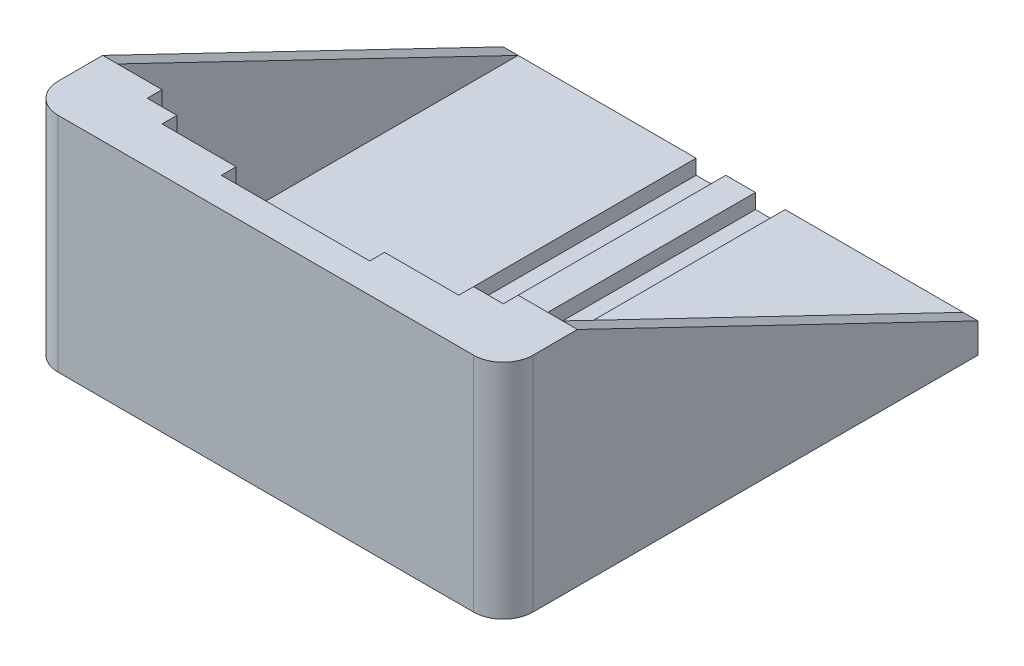
SolidWorks part; units mm, degrees
ref_plane "Front Plane" through (0, 0, 0) normal (0, 0, 1) x (1, 0, 0)
ref_plane "Top Plane" through (0, 0, 0) normal (0, 1, 0) x (1, 0, 0)
ref_plane "Right Plane" through (0, 0, 0) normal (1, 0, 0) x (0, 0, -1)
sketch "Sketch1" plane through (0, 0, 0) normal (0, 1, 0) x (1, 0, 0)
  line L1 (-80, 80) -> (80, 80)
  line L2 (-80, 80) -> (-80, -80)
  line L3 (-80, -80) -> (80, -80)
  line L4 (80, 80) -> (80, -80)
  line L5 (-80, 80) -> (80, -80) construction
  line L6 (-80, -80) -> (80, 80) construction
  point P0 (0, 0)
  dimension "D1" = 160
  dimension "D2" = 160
extrude "Boss-Extrude1" add sketch "Sketch1" along normal blind 75
sketch "Sketch2" plane through (0, 75, 0) normal (0, 1, 0) x (1, 0, 0)
  line L0 (-80, 80) -> (-80, -80) construction
  line L2 (-75, 80) -> (75, 80)
  line L4 (-75, 80) -> (-75, -70)
  line L5 (-75, -70) -> (75, -70)
  line L6 (75, 80) -> (75, -70)
  line L7 (80, -80) -> (80, 80) construction
  line L8 (80, 80) -> (-80, 80) construction
  line L9 (-80, -80) -> (80, -80) construction
  point P6 (0, 0)
  point P13 (0, 0)
  dimension "D1" = 5
  dimension "D2" = 5
  dimension "D3" = 0
  dimension "D4" = 10
extrude "Cut-Extrude1" cut sketch "Sketch2" against normal offset from surface (65 mm away) 10 up to face at (0, 0, 0)
sketch "Sketch3" plane through (0, 0, 70) normal (0, 0, -1) x (-1, 0, 0)
  line L0 (-75, 10) -> (75, 10) construction
  line L1 (-75, 75) -> (-60, 75)
  line L2 (-75, 75) -> (-75, 10)
  line L3 (-75, 10) -> (-60, 10)
  line L4 (-60, 75) -> (-60, 10)
  line L5 (0, 75) -> (0, 10) construction
  line L6 (75, 75) -> (-75, 75) construction
  line L7 (75, 10) -> (60, 10)
  line L8 (60, 75) -> (60, 10)
  line L9 (75, 75) -> (60, 75)
  line L10 (75, 75) -> (75, 10)
  dimension "D1" = 15
extrude "Boss-Extrude2" add sketch "Sketch3" along normal blind 15
sketch "Sketch4" plane through (0, 0, 70) normal (0, 0, -1) x (-1, 0, 0)
  line L0 (0, 75) -> (0, 10) construction
  line L1 (60, 75) -> (-60, 75) construction
  line L2 (75, 10) -> (-75, 10) construction
  line L3 (-60, 10) -> (60, 10) construction
  line L4 (-60, 75) -> (-50, 75)
  line L5 (-60, 75) -> (-60, 10)
  line L6 (-60, 10) -> (-50, 10)
  line L7 (-50, 75) -> (-50, 10)
  line L8 (60, 10) -> (50, 10)
  line L9 (50, 75) -> (50, 10)
  line L10 (60, 75) -> (50, 75)
  line L11 (60, 75) -> (60, 10)
  dimension "D1" = 10
extrude "Boss-Extrude3" add sketch "Sketch4" along normal blind 10
fillet "Fillet1" radius 10 2 edges at (80, 37.5, 80) (-80, 37.5, 80)
sketch "Sketch11" plane through (0, 0, 70) normal (0, 0, -1) x (-1, 0, 0)
  line L0 (-50, 10) -> (50, 10) construction
  line L1 (-50, 75) -> (-25, 75)
  line L2 (-50, 75) -> (-50, 10)
  line L3 (-50, 10) -> (-25, 10)
  line L4 (-25, 75) -> (-25, 10)
  line L5 (0, 75) -> (0, 10) construction
  line L6 (50, 75) -> (-50, 75) construction
  line L7 (75, 10) -> (-75, 10) construction
  line L8 (50, 10) -> (25, 10)
  line L9 (25, 75) -> (25, 10)
  line L10 (50, 75) -> (25, 75)
  line L11 (50, 75) -> (50, 10)
  dimension "D1" = 25
extrude "Boss-Extrude4" add sketch "Sketch11" along normal blind 5
fillet "Fillet2" radius 30 2 edges at (-77.5, 75, -80) (77.5, 75, -80)
sketch "Sketch15" plane through (0, 0, 0) normal (0, -1, 0) x (1, 0, 0)
  line L0 (-80, 40) -> (80, 40) construction
  line L1 (80, 70) -> (80, -80) construction
  line L2 (25, 70) -> (-25, 70) construction
  line L4 (-80, -80) -> (-80, 70) construction
  circle A0 centre (-60, 50) radius 1.5
  circle A1 centre (-40, 50) radius 1.5
  circle A2 centre (40, 50) radius 1.5
  circle A3 centre (60, 50) radius 1.5
  circle A4 centre (60, 30) radius 1.5
  circle A5 centre (40, 30) radius 1.5
  circle A6 centre (-40, 30) radius 1.5
  circle A7 centre (-60, 30) radius 1.5
  point P6 (0, 0)
  dimension "D1" = 3
  dimension "D2" = 3
  dimension "D11" = 3
  dimension "D12" = 3
  dimension "D3" = 20
  dimension "D4" = 10
  dimension "D5" = 20
  dimension "D6" = 10
  dimension "D7" = 10
  dimension "D8" = 20
  dimension "D9" = 20
  dimension "D10" = 30
extrude "Cut-Extrude2" cut sketch "Sketch15" against normal up to surface (10 mm away) up to face at (0, 10, 43.75)
sketch "Sketch17" plane through (0, 10, 0) normal (0, 1, 0) x (1, 0, 0)
  line L0 (80, -70) -> (80, 80) construction
  line L5 (-80, 80) -> (-80, -70) construction
  circle A1 centre (-60, -30) radius 3
  circle A2 centre (-40, -30) radius 3
  circle A3 centre (-40, -50) radius 3
  circle A4 centre (-60, -50) radius 3
  circle A5 centre (40, -50) radius 3
  circle A6 centre (60, -50) radius 3
  circle A7 centre (40, -30) radius 3
  circle A8 centre (60, -30) radius 3
  point P19 (0, 0)
  point P33 (-60, -50)
  dimension "D1" = 20
  dimension "D2" = 6
  dimension "D9" = 6
  dimension "D3" = 20
  dimension "D4" = 20
  dimension "D5" = 0
  dimension "D6" = 20
  dimension "D7" = 20
  dimension "D8" = 20
extrude "Cut-Extrude3" cut sketch "Sketch17" against normal blind 1.5
sketch "Sketch18" plane through (0, 10, 0) normal (0, 1, 0) x (1, 0, 0)
  line L0 (0, 80) -> (0, -70) construction
  line L1 (-75, 80) -> (75, 80) construction
  line L2 (25, -70) -> (-25, -70) construction
  line L3 (-25, -70) -> (25, -70) construction
  line L4 (5, 80) -> (15, 80)
  line L5 (5, 80) -> (5, -65)
  line L6 (5, -65) -> (15, -65)
  line L7 (15, 80) -> (15, -65)
  line L8 (-5, -65) -> (-15, -65)
  line L9 (-15, 80) -> (-15, -65)
  line L10 (-5, 80) -> (-15, 80)
  line L11 (-5, 80) -> (-5, -65)
  dimension "D1" = 10
  dimension "D2" = 0
  dimension "D3" = 10
  dimension "D4" = 5
extrude "Cut-Extrude6" cut sketch "Sketch18" against normal blind 5
sketch "Sketch22" plane through (80, 0, 0) normal (1, 0, 0) x (0, 0, -1)
  line L0 (-55, 75) -> (80, 10)
  line L1 (80, 45) -> (80, 0) construction
  line L2 (-70, 0) -> (80, 0) construction
  line L3 (-55, 75) -> (80, 75)
  line L4 (80, 75) -> (80, 10)
  dimension "D1" = 10
extrude "Cut-Extrude9" cut sketch "Sketch22" against normal through all
fillet "Fillet3" radius 1 7 edges at (-67.5, 10, 55) (-55, 10, 60) (-37.5, 10, 65) (0, 10, 70) (37.5, 10, 65) (55, 10, 60) (67.5, 10, 55)
